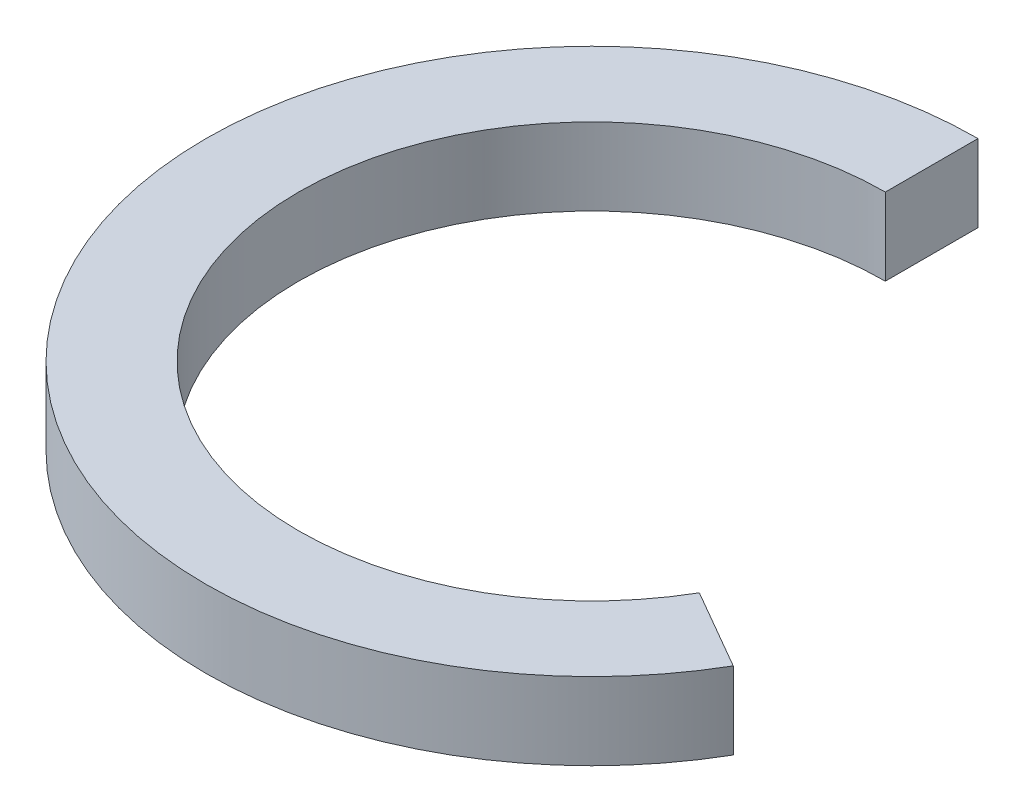
SolidWorks part; units mm, degrees
material "AISI Type 316L stainless steel"
ref_plane "Front Plane" through (0, 0, 0) normal (0, 0, 1) x (1, 0, 0)
ref_plane "Top Plane" through (0, 0, 0) normal (0, 1, 0) x (1, 0, 0)
ref_plane "Right Plane" through (0, 0, 0) normal (1, 0, 0) x (0, 0, -1)
sketch "Sketch1" plane through (0, 0, 0) normal (0, 1, 0) x (1, 0, 0)
  line L0 (0, 60.325) -> (0, 79.375)
  line L1 (68.7408, -39.6875) -> (52.243, -30.1625)
  line L2 (-3.175, 66.3719) -> (-3.175, 72.7484)
  line L3 (55.3791, -46.6378) -> (49.7317, -43.3773)
  arc A0 (0, 79.375) -> (68.7408, -39.6875) centre (0, 0) ccw
  arc A1 (52.243, -30.1625) -> (0, 60.325) centre (0, 0) cw
  arc A2 (-3.175, 72.7484) -> (-6.6261, 75.9114) centre (-6.35, 72.7484) ccw
  arc A3 (-6.6261, 75.9114) -> (56.1303, -51.5347) centre (0, 0) ccw
  arc A4 (56.1303, -51.5347) -> (55.3791, -46.6378) centre (53.7916, -49.3874) ccw
  arc A5 (49.7317, -43.3773) -> (45.8516, -43.9304) centre (48.1442, -46.1269) ccw
  arc A6 (45.8516, -43.9304) -> (-6.0476, 63.2114) centre (0, 0) cw
  arc A7 (-6.0476, 63.2114) -> (-3.175, 66.3719) centre (-6.35, 66.3719) ccw
  point P10 (79.2813, 3.8546)
  point P16 (3.9051, 79.2707)
  point P19 (-31.5594, 50.7072)
  point P20 (77.4372, -16.7348)
  dimension "D1" = 76.2
  dimension "D2" = 3.175
  dimension "D3" = 3.175
  dimension "D4" = 12.7
  dimension "D7" = 3.175
  dimension "D5" = 3.175
  dimension "D6" = 12.7
  dimension "D8" = 120
extrude "Boss-Extrude1" add sketch "Sketch1" along normal blind 3.175 contours A6 A7 L2 A2 A3 A4 L3 A5 | A3 L0 A0 L1 | A4 L1 A1 L0 A2 L2 A7 A6 A5 L3 region at (-54.1233, 0, 31.2481) region at (-5.4966, 0, -65.5963)
extrude "Boss-Extrude2" add sketch "Sketch1<3>" against normal blind 12.7 contours A4 L1 A1 L0 A2 L2 A7 A6 A5 L3 region at (-54.1233, 0, 31.2481)
sketch "Sketch1<3>" plane through (0, 0, 0) normal (0, 1, 0) x (1, 0, 0) same geometry as "Sketch1"
hole_wizard "Pipe Tap Drill for 1/4 Tap1" positions "3DSketch1" profile "Sketch2" hole size "1/4" standard "ANSI Inch"
sketch3d "3DSketch1"
  line L0 (52.243, -12.7, 30.1625) -> (68.7408, 0, 39.6875) construction
  line L2 (68.7408, 3.175, 39.6875) -> (68.7408, -12.7, 39.6875) construction
  line L3 (68.7408, 3.175, 39.6875) -> (68.7408, 0, 39.6875) construction
  point P0 (60.4919, -6.35, 34.925)
  dimension "D1" = 3.175
sketch "Sketch2" plane through (60.4919, -6.35, 34.925) normal (0, 1, 0) x (-0.866, 0, -0.5)
  line L0 (0, 0) -> (0, 19.2173)
  line L1 (0, 19.2173) -> (5.5626, 15.875)
  line L2 (5.5626, 15.875) -> (5.5626, 0)
  line L5 (5.5626, 0) -> (0, 0)
  line L10 (0, 19.2173) -> (-5.5626, 15.875) construction
  line L11 (0, -6.35) -> (0, 107.95) construction
  dimension "Hole Dia." = 11.1252
  dimension "Hole Depth" = 15.875
  dimension "Drill Angle" = 118
